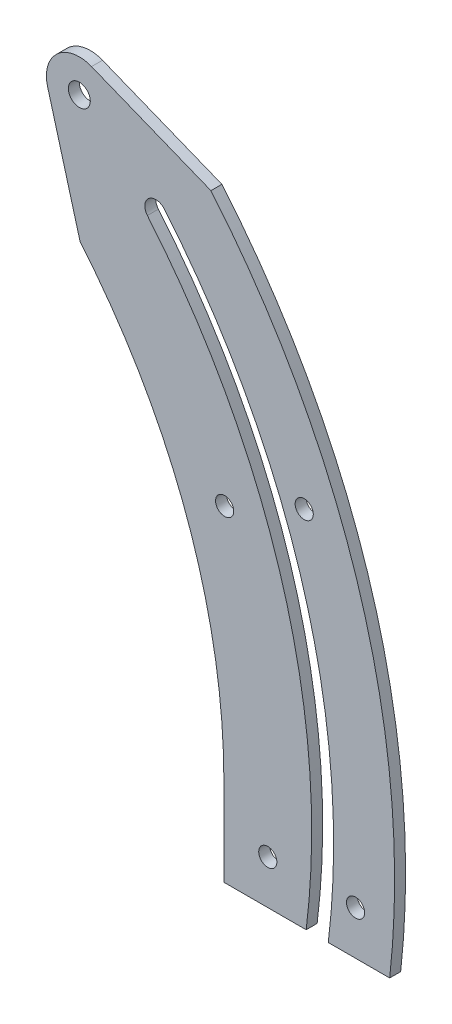
SolidWorks part; units mm, degrees
material "6061-T6 (SS)"
ref_plane "Front Plane" through (0, 0, 0) normal (0, 0, 1) x (1, 0, 0)
ref_plane "Top Plane" through (0, 0, 0) normal (0, 1, 0) x (1, 0, 0)
ref_plane "Right Plane" through (0, 0, 0) normal (1, 0, 0) x (0, 0, -1)
sketch "Sketch2" plane through (0, 0, 0) normal (0, 0, 1) x (1, 0, 0)
  line L12 (155.6602, 130.6144) -> (160.5246, 134.6961)
  line L13 (208.0049, -25.4) -> (225.7757, -25.4)
  line L14 (174.0453, 146.0413) -> (139.5033, 159.8514)
  line L15 (126.7844, 148.4774) -> (136.2027, 114.2876)
  line L16 (177.8, 0) -> (177.8, -25.4)
  line L17 (177.8, -25.4) -> (201.6062, -25.4)
  arc A10 (201.6062, -25.4) -> (155.6602, 130.6144) centre (0, 0) ccw
  arc A11 (208.0049, -25.4) -> (160.5246, 134.6961) centre (0, 0) ccw
  arc A12 (225.7757, -25.4) -> (174.0453, 146.0413) centre (0, 0) ccw
  arc A13 (139.5033, 159.8514) -> (126.7844, 148.4774) centre (135.9673, 151.007) ccw
  arc A14 (177.8, 0) -> (136.2027, 114.2876) centre (0, 0) ccw
extrude "Copied sketch - dont mess with" add sketch "Sketch2" along normal blind 3.175
sketch "Sketch3" plane through (0, 0, 3.175) normal (0, 0, 1) x (1, 0, 0)
  circle A0 centre (135.9673, 151.007) radius 3.175
  dimension "D1" = 6.35
extrude "Hole for top support bracing" cut sketch "Sketch3" against normal through all
sketch "Sketch4" plane through (0, 0, 3.175) normal (0, 0, 1) x (1, 0, 0)
  line L0 (155.6602, 130.6144) -> (160.5246, 134.6961) construction
  circle A0 centre (158.0924, 132.6553) radius 3.175
extrude "Making it machinable" cut sketch "Sketch4" against normal through all
sketch "Sketch5" plane through (0, 0, 3.175) normal (0, 0, 1) x (1, 0, 0)
  line L0 (177.8, -25.4) -> (201.6062, -25.4) construction
  line L2 (190.5, -12.7) -> (215.9, -12.7) construction
  line L3 (178.0189, 68.9987) -> (201.0391, 79.7332) construction
  line L4 (0, 0) -> (177.8, -25.4) construction
  line L5 (0, 0) -> (171.876, 52.1213) construction
  circle A0 centre (190.5, -12.7) radius 2.6289
  circle A1 centre (215.9, -12.7) radius 2.6289
  circle A2 centre (178.0189, 68.9987) radius 2.6289
  circle A3 centre (201.0391, 79.7332) radius 2.6289
  point P6 (177.8, -25.4)
  point P7 (0, 0)
  point P9 (251.595, 63.3066)
  point P14 (171.876, 52.1213)
  point P18 (0, 0)
  dimension "D1" = 12.7
  dimension "D3" = 5.2578
  dimension "D5" = 5.2578
  dimension "D2" = 12.7
  dimension "D4" = 25.4
  dimension "D7" = 25
  dimension "D6" = 2
extrude "Cut-Extrude1" cut sketch "Sketch5" against normal through all both
